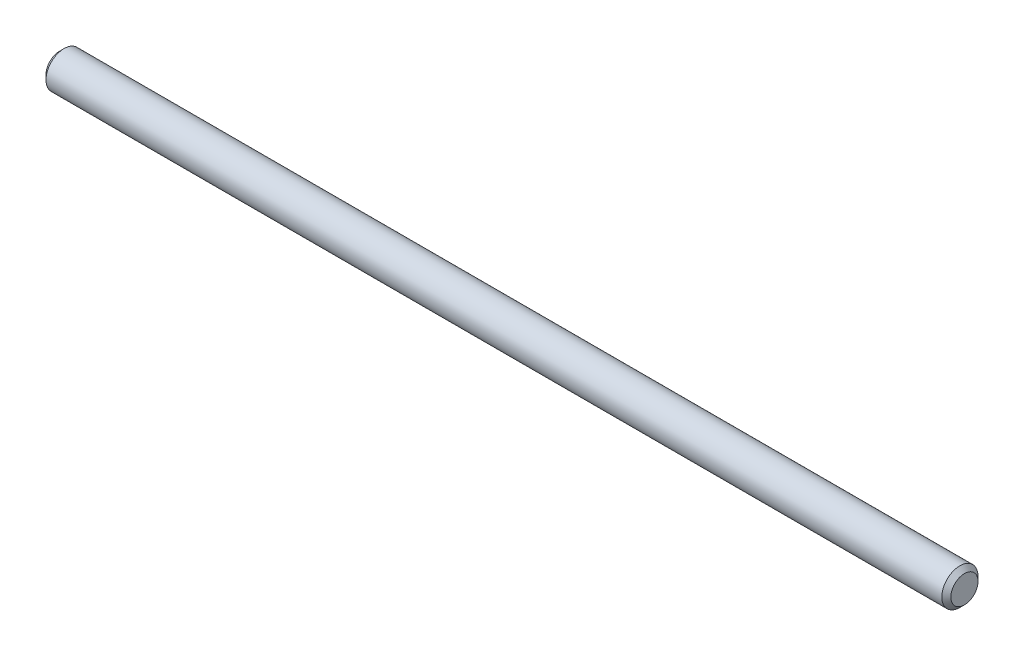
SolidWorks part; units mm, degrees
ref_plane "Alzado" through (0, 0, 0) normal (0, 0, 1) x (1, 0, 0)
ref_plane "Planta" through (0, 0, 0) normal (0, 1, 0) x (1, 0, 0)
ref_plane "Vista lateral" through (0, 0, 0) normal (1, 0, 0) x (0, 0, -1)
sketch "Croquis1" plane through (0, 0, 0) normal (1, 0, 0) x (0, 0, -1)
  circle A0 centre (0, 0) radius 4
  dimension "D1" = 8
extrude "Saliente-Extruir1" add sketch "Croquis1" along normal blind 200
cosmetic thread "Rosca cosmética3" parameters "D1"=198.9999, "D2"=6.891
cosmetic thread "Rosca cosmética4" parameters "D2"=6.891
chamfer "Chaflán1" distance 1 angle 45 1 edges at (200, 0, -4)
chamfer "Chaflán2" distance 1 angle 45 1 edges at (0, 0, -4)
